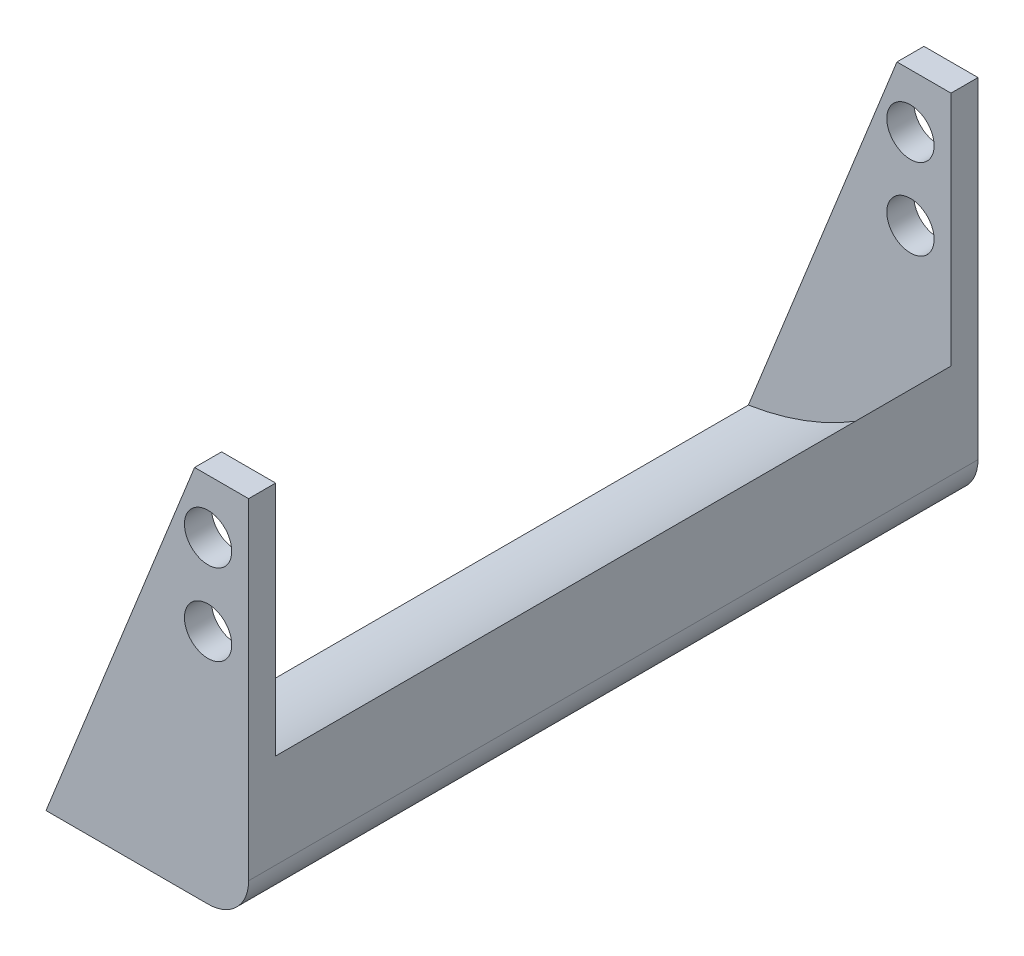
SolidWorks part; units mm, degrees
ref_plane "Front Plane" through (0, 0, 0) normal (0, 0, 1) x (1, 0, 0)
ref_plane "Top Plane" through (0, 0, 0) normal (0, 1, 0) x (1, 0, 0)
ref_plane "Right Plane" through (0, 0, 0) normal (1, 0, 0) x (0, 0, -1)
sketch "Sketch1" plane through (0, 0, 0) normal (0, 0, 1) x (1, 0, 0)
  line L0 (0, 0) -> (15, 0)
  line L1 (15, 0) -> (15, 10)
  arc A0 (0, 0) -> (15, 10) centre (-3.3273, 21.241) ccw
  dimension "D3" = 21.5
  dimension "D1" = 10
  dimension "D2" = 15
extrude "Boss-Extrude1" add sketch "Sketch1" along normal mid plane 50
sketch "Sketch2" plane through (0, 0, 25) normal (0, 0, 1) x (1, 0, 0)
  line L0 (15, 0) -> (15, 27.5)
  line L1 (15, 27.5) -> (11, 27.5)
  line L2 (11, 27.5) -> (0, 0)
  line L3 (0, 0) -> (15, 0)
  line L4 (12, 27.5) -> (12, 23.5) construction
  line L5 (12, 23.5) -> (12, 17.5) construction
  circle A0 centre (12, 23.5) radius 1.75
  circle A1 centre (12, 17.5) radius 1.75
  dimension "D5" = 3.5
  dimension "D1" = 27.5
  dimension "D2" = 4
  dimension "D3" = 4
  dimension "D4" = 6
  dimension "D6" = 3
extrude "Boss-Extrude2" add sketch "Sketch2" along normal blind 2
mirror "Mirror1" about plane through (0, 0, 0) normal (0, 0, 1) of "Boss-Extrude2"
fillet "Fillet1" radius 3 1 edges at (15, 0, 0)
